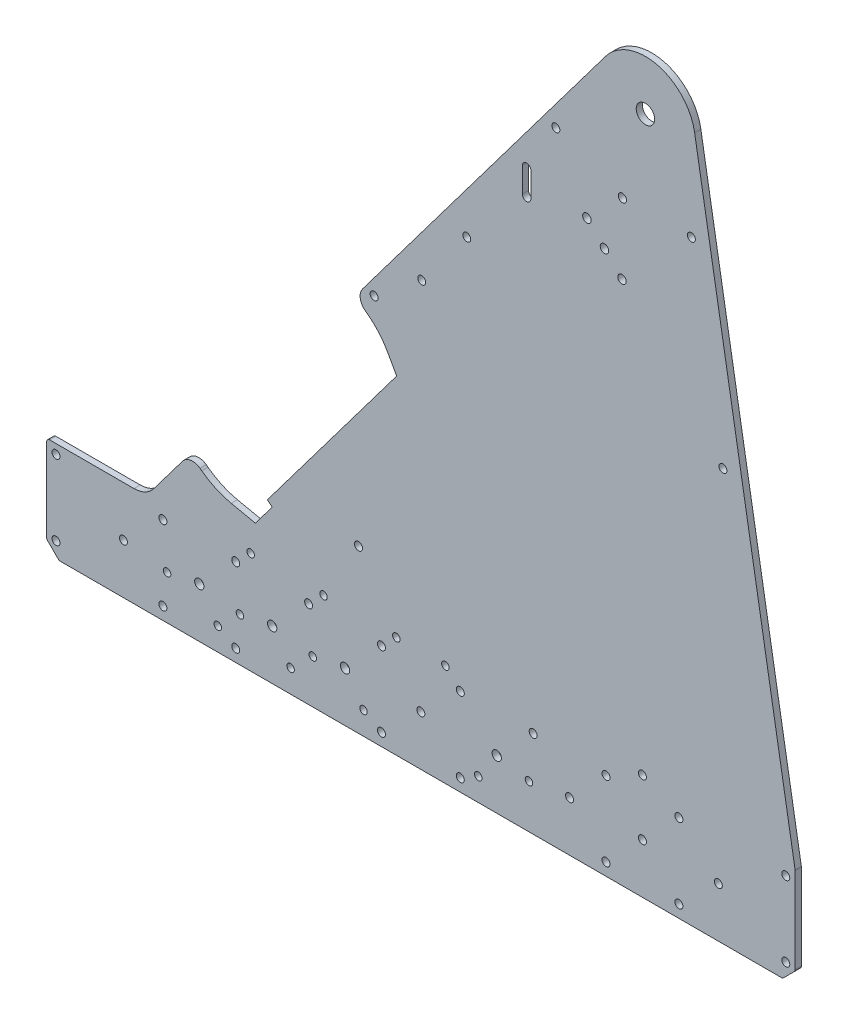
SolidWorks part; units mm, degrees
ref_plane "Front Plane" through (0, 0, 0) normal (0, 0, 1) x (1, 0, 0)
ref_plane "Top Plane" through (0, 0, 0) normal (0, 1, 0) x (1, 0, 0)
ref_plane "Right Plane" through (0, 0, 0) normal (1, 0, 0) x (0, 0, -1)
sketch "Sketch1" plane through (0, 0, 0) normal (0, 0, 1) x (1, 0, 0)
  line L1 (0, 0) -> (381, 0)
  line L2 (0, 0) -> (0, 50.8)
  line L4 (381, 0) -> (381, 50.8)
  line L5 (381, 50.8) -> (329.8374, 350.3513)
  line L6 (0, 50.8) -> (44.463, 50.8)
  line L7 (54.6105, 55.8634) -> (73.025, 80.3327)
  line L9 (112.3265, 79.755) -> (178.1676, 167.245)
  line L11 (157.0275, 191.9556) -> (284.5049, 361.3482)
  line L12 (112.3265, 79.755) -> (114.8634, 77.8458)
  line L13 (114.8634, 77.8458) -> (106.2722, 66.4299)
  line L14 (157.0275, 191.9556) -> (169.7119, 182.4098)
  line L15 (169.7119, 182.4098) -> (178.1676, 167.245)
  line L16 (73.025, 80.3327) -> (85.7094, 70.7869)
  line L17 (85.7094, 70.7869) -> (106.2722, 66.4299)
  line L18 (169.7119, 182.4098) -> (85.7094, 70.7869) construction
  arc A0 (284.5049, 361.3482) -> (329.8374, 350.3513) centre (304.8, 346.075) cw
  arc A1 (44.463, 50.8) -> (54.6105, 55.8634) centre (44.463, 63.5) ccw
  point P11 (50.8, 50.8)
  dimension "D4" = 346.075
  dimension "D7" = 12.7
  dimension "D5" = 25.4
  dimension "D1" = 50.8
  dimension "D2" = 381
  dimension "D3" = 76.2
  dimension "D6" = 50.8
  dimension "D8" = 123.825
  dimension "D9" = 139.7
  dimension "D10" = 15.875
  dimension "D11" = 31.75
  dimension "D12" = 73.025
  dimension "D13" = 3.175
  dimension "D14" = 14.2875
  dimension "D15" = 115
extrude "Boss-Extrude1" add sketch "Sketch1" along normal blind 3.175
sketch "Sketch2" plane through (0, 0, 3.175) normal (0, 0, 1) x (1, 0, 0)
  line L1 (190.5, 50.8) -> (190.5, 0) construction
  line L3 (0, 0) -> (381, 0) construction
  line L5 (0, 6.35) -> (0, 0)
  line L6 (0, 50.8) -> (0, 0) construction
  line L7 (0, 0) -> (6.35, 0)
  line L8 (6.35, 0) -> (0, 6.35)
  line L9 (381, 0) -> (374.65, 0)
  line L10 (374.65, 0) -> (381, 6.35)
  line L11 (381, 6.35) -> (381, 0)
  circle A19 centre (4.7625, 46.0375) radius 2.032
  circle A20 centre (4.7625, 7.9375) radius 2.032
  circle A21 centre (376.2375, 7.9375) radius 2.032
  circle A22 centre (376.2375, 46.0375) radius 2.032
  dimension "D21" = 6.35
  dimension "D27" = 4.064
  dimension "D4" = 46.0375
  dimension "D22" = 6.35
  dimension "D25" = 4.7625
  dimension "D28" = 7.9375
extrude "Cut-Extrude1" cut sketch "Sketch2" against normal up to next
sketch "Sketch5" plane through (0, 0, 3.175) normal (0, 0, 1) x (1, 0, 0)
  line L0 (151.892, 25.4) -> (229.108, 25.4) construction
  line L1 (229.108, 25.4) -> (341.884, 25.4) construction
  circle A0 centre (39.116, 25.4) radius 2.032
  circle A1 centre (59.182, 6.35) radius 2.032
  circle A2 centre (59.182, 44.45) radius 2.032
  circle A3 centre (96.266, 44.45) radius 2.032
  circle A4 centre (133.35, 44.45) radius 2.032
  circle A5 centre (170.434, 44.45) radius 2.032
  circle A6 centre (210.566, 44.45) radius 2.032
  circle A7 centre (210.566, 6.35) radius 2.032
  circle A8 centre (170.434, 6.35) radius 2.032
  circle A9 centre (247.65, 44.45) radius 2.032
  circle A10 centre (266.192, 25.4) radius 2.032
  circle A11 centre (39.116, 25.4) radius 2.286 construction
  circle A12 centre (59.182, 44.45) radius 1.905 construction
  circle A13 centre (59.182, 6.35) radius 1.905 construction
  circle A14 centre (96.266, 44.45) radius 1.905 construction
  circle A15 centre (133.35, 44.45) radius 1.905 construction
  circle A16 centre (170.434, 44.45) radius 1.905 construction
  circle A17 centre (170.434, 6.35) radius 2.159 construction
  circle A18 centre (210.566, 6.35) radius 2.159 construction
  circle A19 centre (210.566, 44.45) radius 1.905 construction
  circle A20 centre (247.65, 44.45) radius 1.905 construction
  circle A21 centre (266.192, 25.4) radius 2.286 construction
  circle A22 centre (77.724, 25.4) radius 2.3813
  circle A23 centre (114.808, 25.4) radius 2.3813
  circle A24 centre (151.892, 25.4) radius 2.3813
  circle A25 centre (229.108, 25.4) radius 2.3813
  circle A26 centre (190.5, 25.4) radius 2.032
  circle A28 centre (303.276, 25.4) radius 2.032
  circle A29 centre (341.884, 25.4) radius 2.032
  circle A30 centre (77.724, 25.4) radius 7.366 construction
  circle A31 centre (114.808, 25.4) radius 7.366 construction
  circle A32 centre (151.892, 25.4) radius 7.366 construction
  circle A33 centre (229.108, 25.4) radius 7.366 construction
  dimension "D1" = 4.064
  dimension "D2" = 4.7625
  dimension "D3" = 37.084
  dimension "D4" = 38.608
  dimension "D5" = 38.608
extrude "Cut-Extrude4" cut sketch "Sketch5" against normal through all
sketch "Sketch6" plane through (0, 0, 3.175) normal (0, 0, 1) x (1, 0, 0)
  line L0 (6.35, 0) -> (374.65, 0) construction
  line L1 (266.192, 25.4) -> (303.276, 25.4) construction
  line L2 (284.734, 6.35) -> (284.734, 44.45) construction
  line L3 (151.892, 25.4) -> (114.808, 25.4) construction
  line L4 (114.808, 25.4) -> (77.724, 25.4) construction
  circle A0 centre (284.734, 44.45) radius 2.032
  circle A1 centre (284.734, 6.35) radius 2.032
  circle A2 centre (321.818, 6.35) radius 2.032
  circle A3 centre (321.818, 44.45) radius 2.032
  circle A4 centre (96.266, 6.35) radius 2.032
  circle A6 centre (303.276, 53.975) radius 2.032
  arc A7 (304.329, 52.3875) -> (302.223, 52.3875) centre (303.276, 53.975) ccw construction
  point P8 (284.734, 25.4)
  point P9 (284.734, 25.4)
  point P28 (96.266, 25.4)
  dimension "D1" = 4.064
  dimension "D2" = 6.35
  dimension "D3" = 37.084
extrude "Cut-Extrude5" cut sketch "Sketch6" against normal through all
sketch "Sketch3" plane through (0, 0, 3.175) normal (0, 0, 1) x (1, 0, 0)
  line L0 (73.025, 80.3327) -> (54.6105, 55.8634) construction
  line L1 (381, 6.35) -> (381, 50.8) construction
  line L2 (6.35, 0) -> (374.65, 0) construction
  line L3 (304.8, 346.075) -> (293.0652, 303.202) construction
  line L4 (275.0085, 285.3381) -> (293.0652, 303.202) construction
  line L5 (275.0085, 285.3381) -> (283.9404, 276.3098) construction
  line L6 (283.9404, 276.3098) -> (292.8724, 267.2815) construction
  line L7 (381, 50.8) -> (329.8374, 350.3513) construction
  line L8 (244.3127, 279.4) -> (244.3127, 292.1) construction
  line L9 (0, 50.8) -> (0, 6.35) construction
  line L12 (284.5049, 361.3482) -> (157.0275, 191.9556) construction
  line L13 (242.1537, 279.4) -> (242.1537, 292.1)
  line L14 (246.4717, 279.4) -> (246.4717, 292.1)
  line L15 (190.9415, 215.9) -> (213.8513, 246.3426) construction
  circle A0 centre (304.8, 346.075) radius 4.699
  circle A1 centre (166.6875, 196.85) radius 2.032
  circle A2 centre (158.75, 82.55) radius 2.032
  circle A3 centre (293.0652, 303.202) radius 2.0955
  circle A5 centre (275.0085, 285.3381) radius 2.159
  circle A6 centre (283.9404, 276.3098) radius 2.159
  circle A7 centre (292.8724, 267.2815) radius 2.159
  circle A8 centre (328.1868, 303.4404) radius 2.032
  circle A9 centre (344.223, 209.55) radius 2.032
  circle A12 centre (259.2118, 317.1783) radius 2.032
  arc A26 (242.1537, 279.4) -> (246.4717, 279.4) centre (244.3127, 279.4) ccw
  arc A27 (246.4717, 292.1) -> (242.1537, 292.1) centre (244.3127, 292.1) ccw
  circle A28 centre (213.8513, 246.3426) radius 2.032
  circle A29 centre (190.9415, 215.9) radius 2.032
  point P27 (244.3127, 285.75)
  dimension "D1" = 9.398
  dimension "D3" = 4.064
  dimension "D6" = 4.064
  dimension "D11" = 4.318
  dimension "D10" = 4.191
  dimension "D13" = 4.064
  dimension "D20" = 4.064
  dimension "D18" = 2.159
  dimension "D28" = 12.7
  dimension "D21" = 38.1
  dimension "D19" = 9.525
  dimension "D29" = 4.064
  dimension "D4" = 222.25
  dimension "D5" = 82.55
  dimension "D7" = 25.4
  dimension "D8" = 12.7
  dimension "D9" = 44.45
  dimension "D12" = 12.7
  dimension "D14" = 9.525
  dimension "D15" = 9.525
  dimension "D16" = 95.25
  dimension "D17" = 209.55
  dimension "D22" = 12.7
  dimension "D23" = 53.975
  dimension "D24" = 6.35
  dimension "D25" = 196.85
  dimension "D26" = 166.6875
  dimension "D27" = 279.4
  dimension "D30" = 25
  dimension "D31" = 150
  dimension "D32" = 215.9
extrude "Cut-Extrude2" cut sketch "Sketch3" against normal through all
fillet "Fillet1" radius 1.5875 6 edges at (374.65, 0, 1.5875) (381, 6.35, 1.5875) (381, 50.8, 1.5875) (6.35, 0, 1.5875) (0, 6.35, 1.5875) (0, 50.8, 1.5875)
sketch "Sketch4" plane through (0, 0, 0) normal (0, 0, -1) x (-1, 0, 0)
  circle A0 centre (-61.3181, 22.2981) radius 1.905 construction
  circle A1 centre (-87.1313, 11.606) radius 1.905 construction
  circle A2 centre (-98.4021, 22.2981) radius 1.905 construction
  circle A3 centre (-124.2153, 11.606) radius 1.905 construction
  circle A4 centre (-135.4861, 22.2981) radius 1.905 construction
  circle A5 centre (-161.2993, 11.606) radius 1.905 construction
  circle A6 centre (-245.5139, 22.2981) radius 1.905 construction
  circle A7 centre (-219.7007, 11.606) radius 1.905 construction
  circle A8 centre (-202.982, 51.9684) radius 1.905 construction
  circle A9 centre (-178.018, 51.9684) radius 1.905 construction
  circle A10 centre (-140.934, 51.9684) radius 1.905 construction
  circle A11 centre (-103.85, 51.9684) radius 1.905 construction
  circle A12 centre (-61.3181, 22.2981) radius 1.905
  circle A13 centre (-87.1313, 11.606) radius 1.905
  circle A14 centre (-98.4021, 22.2981) radius 1.905
  circle A15 centre (-124.2153, 11.606) radius 1.905
  circle A16 centre (-135.4861, 22.2981) radius 1.905
  circle A17 centre (-161.2993, 11.606) radius 1.905
  circle A18 centre (-245.5139, 22.2981) radius 1.905
  circle A19 centre (-219.7007, 11.606) radius 1.905
  circle A20 centre (-202.982, 51.9684) radius 1.905
  circle A21 centre (-178.018, 51.9684) radius 1.905
  circle A22 centre (-140.934, 51.9684) radius 1.905
  circle A23 centre (-103.85, 51.9684) radius 1.905
extrude "Cut-Extrude3" cut sketch "Sketch4" against normal up to next
fillet "Fillet2" radius 38.1 2 edges at (85.7094, 70.7869, 1.5875) (169.7119, 182.4098, 1.5875)
fillet "Fillet3" radius 6.35 2 edges at (73.025, 80.3327, 1.5875) (157.0275, 191.9556, 1.5875)
